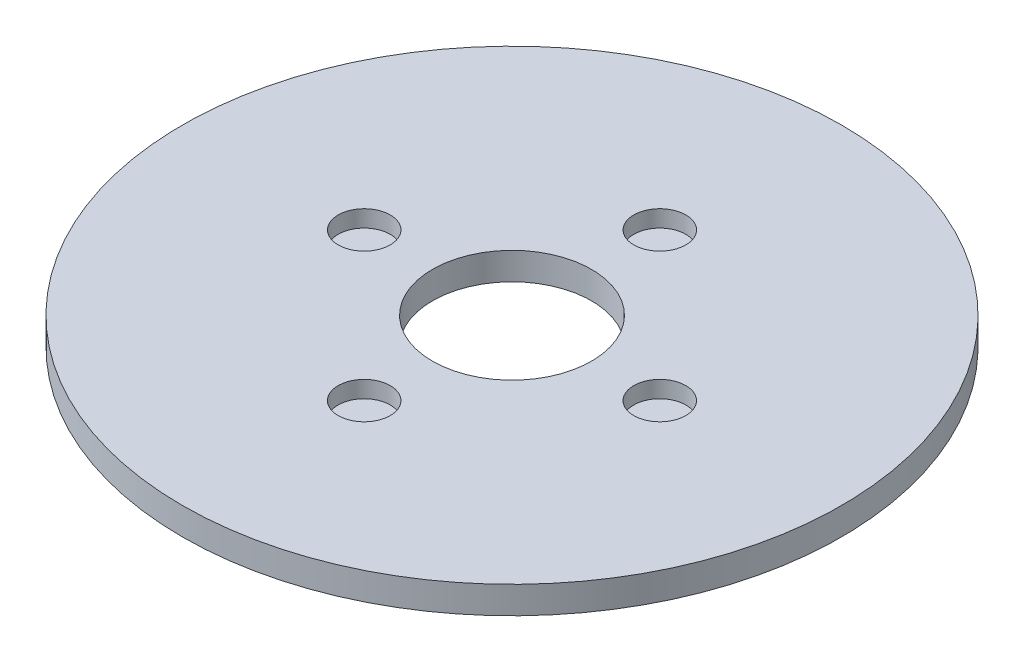
SolidWorks part; units mm, degrees
ref_plane "Front Plane" through (0, 0, 0) normal (0, 0, 1) x (1, 0, 0)
ref_plane "Top Plane" through (0, 0, 0) normal (0, 1, 0) x (1, 0, 0)
ref_plane "Right Plane" through (0, 0, 0) normal (1, 0, 0) x (0, 0, -1)
sketch "Sketch1" plane through (0, 0, 0) normal (0, 1, 0) x (1, 0, 0)
  circle A0 centre (0, 0) radius 72.5
  dimension "FLANGE_OD" = 145
extrude "Boss-Extrude1" add sketch "Sketch1" along normal blind 6
sketch "Sketch2" plane through (0, 0, 0) normal (0, 1, 0) x (1, 0, 0)
  circle A0 centre (0, 0) radius 17.5
  dimension "BORE_D" = 35
extrude "Cut-Extrude1" cut sketch "Sketch2" along normal through all
sketch "Sketch3" plane through (0, 6, 0) normal (0, 1, 0) x (1, 0, 0)
  circle A0 centre (0, 0) radius 32.5149 construction
  circle A1 centre (-32.5149, 0) radius 5.721
  dimension "BOLT_D" = 11.442
  dimension "BOLT_PCD" = 65.0299
extrude "Cut-Extrude2" cut sketch "Sketch3" against normal blind 3.6946
pattern_circular "CirPattern1" count 4 over 360 about axis through (0, 0, 0) along (0, 1, 0) of "Cut-Extrude2"
